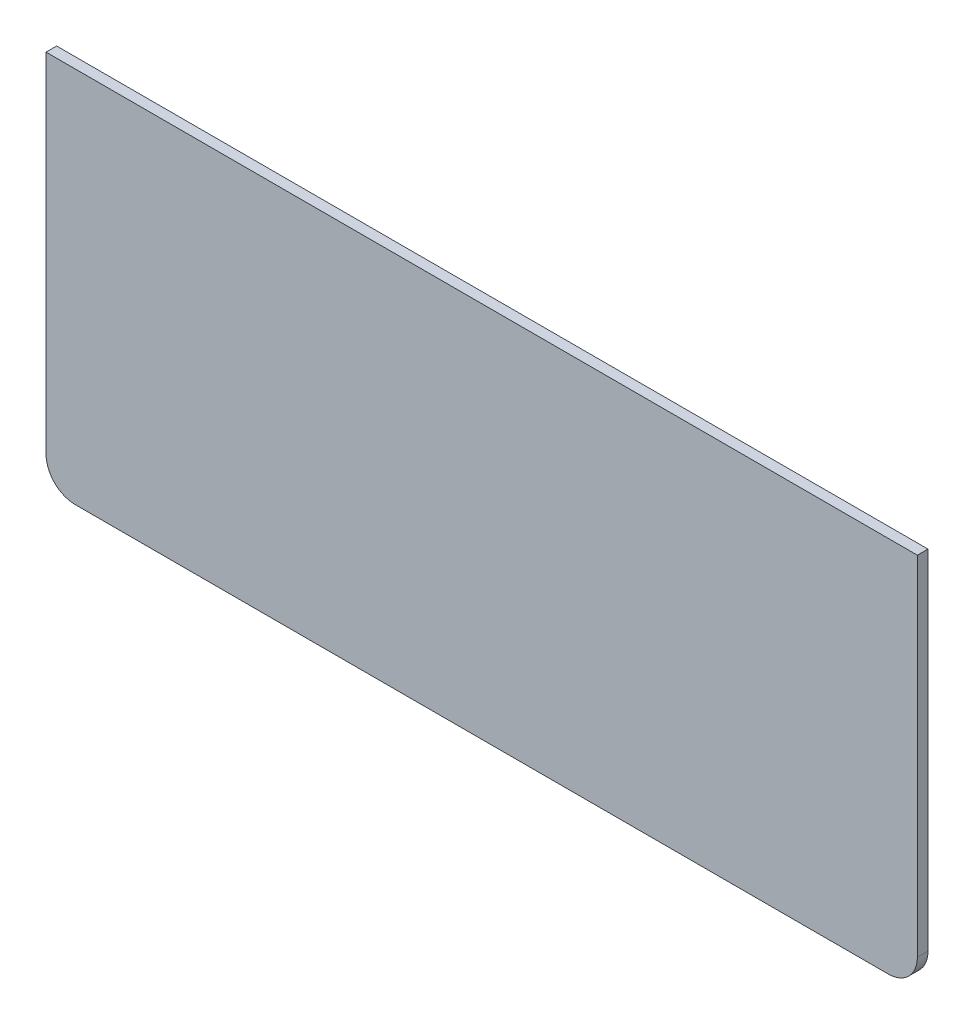
SolidWorks part; units mm, degrees
material "5052-H32"
ref_plane "Front Plane" through (0, 0, 0) normal (0, 0, 1) x (1, 0, 0)
ref_plane "Top Plane" through (0, 0, 0) normal (0, 1, 0) x (1, 0, 0)
ref_plane "Right Plane" through (0, 0, 0) normal (1, 0, 0) x (0, 0, -1)
sketch "Sketch2" plane through (0, 0, 0) normal (0, 0, 1) x (1, 0, 0)
  line L0 (-53.5866, 40.5355) -> (207.7634, 40.5355)
  line L1 (207.7634, 40.5355) -> (207.7634, -72.6395)
  line L2 (207.7634, -72.6395) -> (-53.5866, -72.6395)
  line L3 (-53.5866, -72.6395) -> (-53.5866, 40.5355)
  dimension "D1" = 113.175
  dimension "D2" = 261.35
extrude "Boss-Extrude1" add sketch "Sketch2" along normal blind 3.175
fillet "Fillet1" radius 8.7312 2 edges at (-53.5866, -72.6395, 1.5875) (207.7634, -72.6395, 1.5875)
equation "\"L\"= 400"
equation "\"W\"= 255"
equation "\"H\"= 110"
equation "\"Compartment Width\"= 80"
equation "\"T\"= 4.7625 * 2 / 3"
equation "\"Inside Fillet Radius\"= 5.55625"
equation "\"D1@Fillet1\"=\"Inside Fillet Radius\"+\"T\""
equation "\"D1@Sketch2\"=\"T\"+\"H\""
equation "\"D2@Sketch2\"=2*\"T\"+\"W\""
equation "\"D1@Boss-Extrude1\"=\"T\""
equation "\"Offset\"= 30"
equation "\"Hole\"=15"
equation "\"Wheel to Wall\"= 50"
